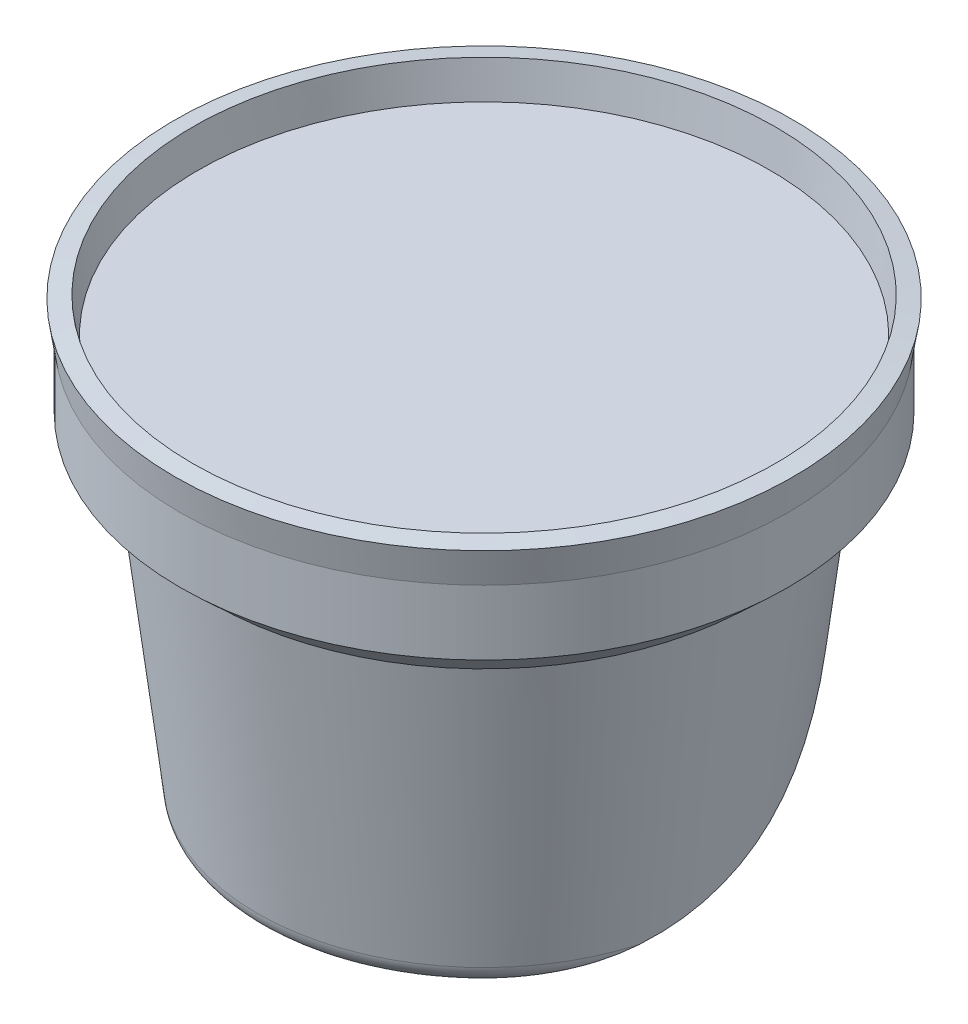
SolidWorks part; units mm, degrees
material "ABS"
ref_plane "Alzado" through (0, 0, 0) normal (0, 0, 1) x (1, 0, 0)
ref_plane "Planta" through (0, 0, 0) normal (0, 1, 0) x (1, 0, 0)
ref_plane "Vista lateral" through (0, 0, 0) normal (1, 0, 0) x (0, 0, -1)
sketch "Sketch2" plane through (0, 0, 0) normal (1, 0, 0) x (0, 0, -1)
  line L0 (-84.4541, -346.164) -> (377.5459, -346.164) construction
  line L1 (0, 0) -> (69.15, 0) construction
  line L2 (0, 0) -> (0, -100) construction
  line L3 (69.15, 0) -> (68, -7.5)
  line L4 (68, -7.5) -> (68, -22)
  line L5 (68, -22) -> (60.5, -29)
  line L6 (60.5, -29) -> (58.5, -29)
  line L7 (58.5, -29) -> (50, -100)
  line L9 (0, 0) -> (0, -100) construction
  line L10 (65.1962, 0.6062) -> (64, -7.1951)
  line L11 (64, -9.1951) -> (64, -20.2618)
  line L12 (64, -20.2618) -> (58.9233, -25)
  line L13 (58.9233, -25) -> (54.9503, -25)
  line L14 (54.9503, -25) -> (45.9714, -100)
  line L16 (69.15, 0) -> (65.1962, 0.6062)
  line L18 (64, -7.1951) -> (0, -7.1951)
  line L19 (0, -7.1951) -> (0, -9.1951)
  line L20 (0, -9.1951) -> (64, -9.1951)
  line L21 (64, -7.1951) -> (64, -20.2618) construction
  line L22 (50, -100) -> (0, -100) construction
  line L23 (46.4503, -96) -> (0, -96) construction
  line L24 (50, -100) -> (45.9714, -100)
  line L25 (54.9503, -25) -> (46.4503, -96) construction
  dimension "D1" = 69.15
  dimension "D2" = 136
  dimension "D3" = 7.5
  dimension "D4" = 22
  dimension "D5" = 29
  dimension "D6" = 121
  dimension "D7" = 117
  dimension "D8" = 100
  dimension "D9" = 100
  dimension "D11" = 2
  dimension "D10" = 4
revolve "Revolve1" add sketch "Sketch2" angle 360 about L9
sketch "Sketch3" plane through (0, 0, 0) normal (1, 0, 0) x (0, 0, -1)
sketch "Sketch4" plane through (0, 0, 0) normal (1, 0, 0) x (0, 0, -1)
  line L0 (58.5, -29) -> (50, -100) construction
  line L1 (-46.0159, -98.1527) -> (-51.0159, -98.1527)
  line L2 (-51.0159, -98.1527) -> (-51.0159, -100)
  line L4 (-51.0159, -100) -> (50, -100)
  line L5 (50, -100) -> (57.6602, -36.0145)
  spline S0 degree 3 poles (-46.0159, -98.1527) (-25.149, -96.7842) (9.5122, -91.4167) (41.0845, -60.9423) (49.3337, -41.2434) (57.6602, -36.0145) knots 0 0 0 0 0.505126 0.77875 1 1 1 1
  dimension "D1" = 15.5775
  dimension "D2" = 40.4834
  dimension "D3" = 49.5807
  dimension "D4" = 57.6602
  dimension "D5" = 20.2153
  dimension "D6" = 46.0159
  dimension "D7" = 5
  dimension "D8" = 43.6173
  dimension "D9" = 57.9344
  dimension "D10" = 82.0946
  dimension "D11" = 95.0695
  dimension "D12" = 1.8473
extrude "Extrude1" cut sketch "Sketch4" against normal through all both and the other way through all
sketch "Sketch5" plane through (0, 0, 0) normal (1, 0, 0) x (0, 0, -1)
  line L0 (0, 0) -> (0, -100) construction
  line L1 (0, -23) -> (0, -123)
  arc A0 (0, -23) -> (0, -123) centre (0, -73) ccw
  dimension "D1" = 100
  dimension "D2" = 73
revolve "Cut-Revolve1" cut sketch "Sketch5" angle 360 about L1
fillet "Fillet4" radius 5 1 edges at (0, -98.1527, 50.2212)
